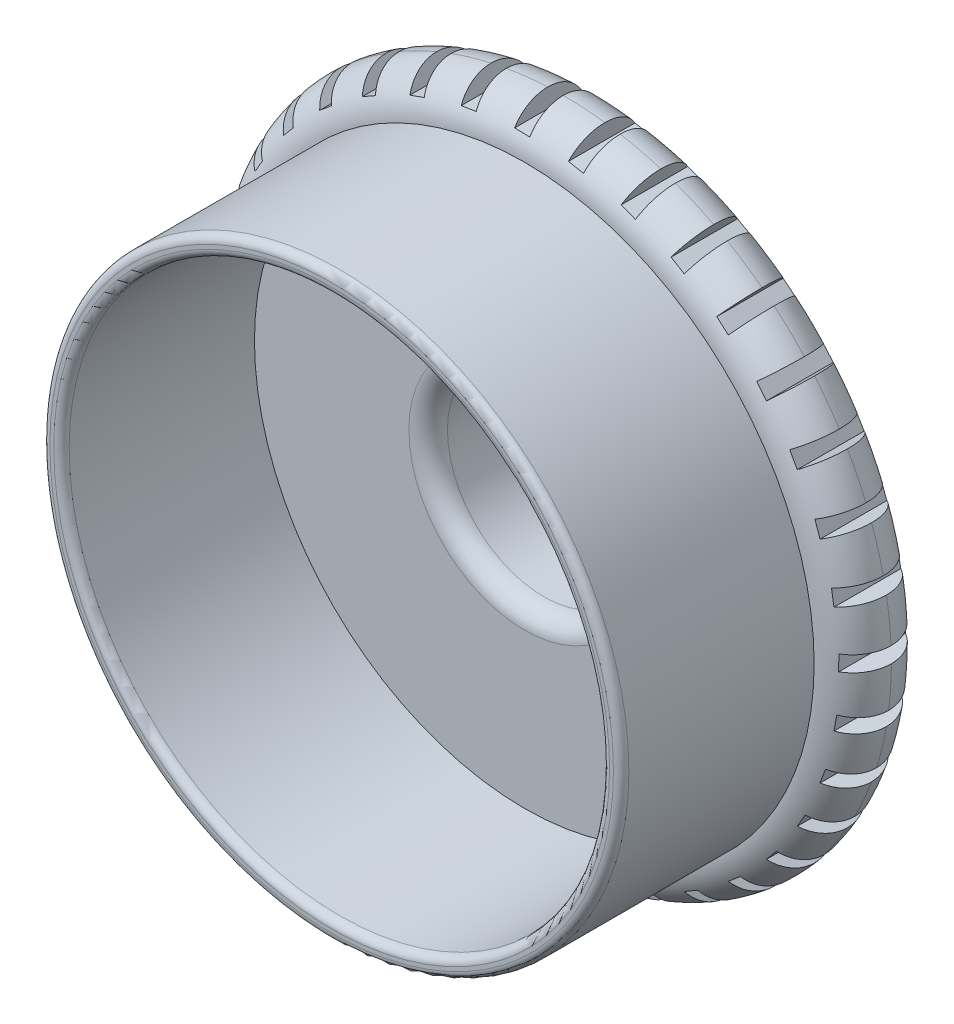
SolidWorks part; units mm, degrees
material "Mosaz"
ref_plane "Přední rovina" through (0, 0, 0) normal (0, 0, 1) x (1, 0, 0)
ref_plane "Horní rovina" through (0, 0, 0) normal (0, 1, 0) x (1, 0, 0)
ref_plane "Pravá rovina" through (0, 0, 0) normal (1, 0, 0) x (0, 0, -1)
sketch "Skica1" plane through (0, 0, 0) normal (0, 0, 1) x (1, 0, 0)
  circle A0 centre (0, 0) radius 7.5
  circle A1 centre (0, 0) radius 7
  dimension "D1" = 15
  dimension "D2" = 14
extrude "Přidat vysunutím1" add sketch "Skica1" against normal blind 5
cosmetic thread "Kosmetický závit1" parameters "D1"=5, "D2"=16
sketch "Skica2" plane through (0, 0, -5) normal (0, 0, -1) x (-1, 0, 0)
  circle A0 centre (0, 0) radius 8.5
  dimension "D1" = 17
extrude "Přidat vysunutím2" add sketch "Skica2" along normal blind 2
fillet "Zaoblit1" radius 1 2 edges at (-8.5, 0, -5) (-8.5, 0, -7)
sketch "Skica3" plane through (0, 0, 0) normal (0, 1, 0) x (1, 0, 0)
  line L0 (-7.5, 7) -> (-5.5, 7.3765)
  line L1 (-5.5, 7.3765) -> (0, 7.3765)
  line L2 (0, 7.3765) -> (0, 7)
  line L3 (7.5, 7) -> (-7.5, 7) construction
  line L4 (0, 7) -> (-7.5, 7)
  dimension "D1" = 5.5
  dimension "D2" = 2
revolve "Rotovat1" add sketch "Skica3" angle 360 about L2
sketch "Skica4" plane through (0, 0, -7.3765) normal (0, 0, -1) x (-1, 0, 0)
  circle A0 centre (0, 0) radius 2.5
  dimension "D1" = 5
extrude "Odebrat vysunutím1" cut sketch "Skica4" against normal through all
fillet "Zaoblit2" radius 0.2 2 edges at (7, 0, 0) (7.5, 0, 0)
fillet "Zaoblit3" radius 0.5 1 edges at (-2.5, 0, -7.3765)
fillet "Zaoblit4" radius 0.5 1 edges at (-2.5, 0, -5)
ref_plane "Rovina1" through (8.5, 0, 0) normal (1, 0, 0) x (0, 0, -1)
sketch "Skica5" plane through (8.5, 0, 0) normal (1, 0, 0) x (0, 0, -1)
  line L0 (5, 0) -> (5, 0.4)
  line L1 (5, 0) -> (7, 0)
  line L2 (7, 0) -> (7, 0.4)
  line L3 (5, 0.4) -> (7, 0.4)
  line L4 (7.3765, 0) -> (2.1573, 0) construction
  line L5 (7.3765, -5.5) -> (7.3765, 5.5) construction
  line L6 (7, 0.8972) -> (7, -1.122) construction
  line L7 (7, 7.5) -> (7, -7.5) construction
  dimension "D1" = 2
  dimension "D2" = 0.4
extrude "Odebrat vysunutím2" cut sketch "Skica5" against normal blind 0.5
ref_axis "Osa1" through (0, 0, -5) along (0, 0, 1)
pattern_circular "Kruhové pole1" count 36 every 10 about axis through (0, 0, -5) along (0, 0, 1) of "Odebrat vysunutím2"
